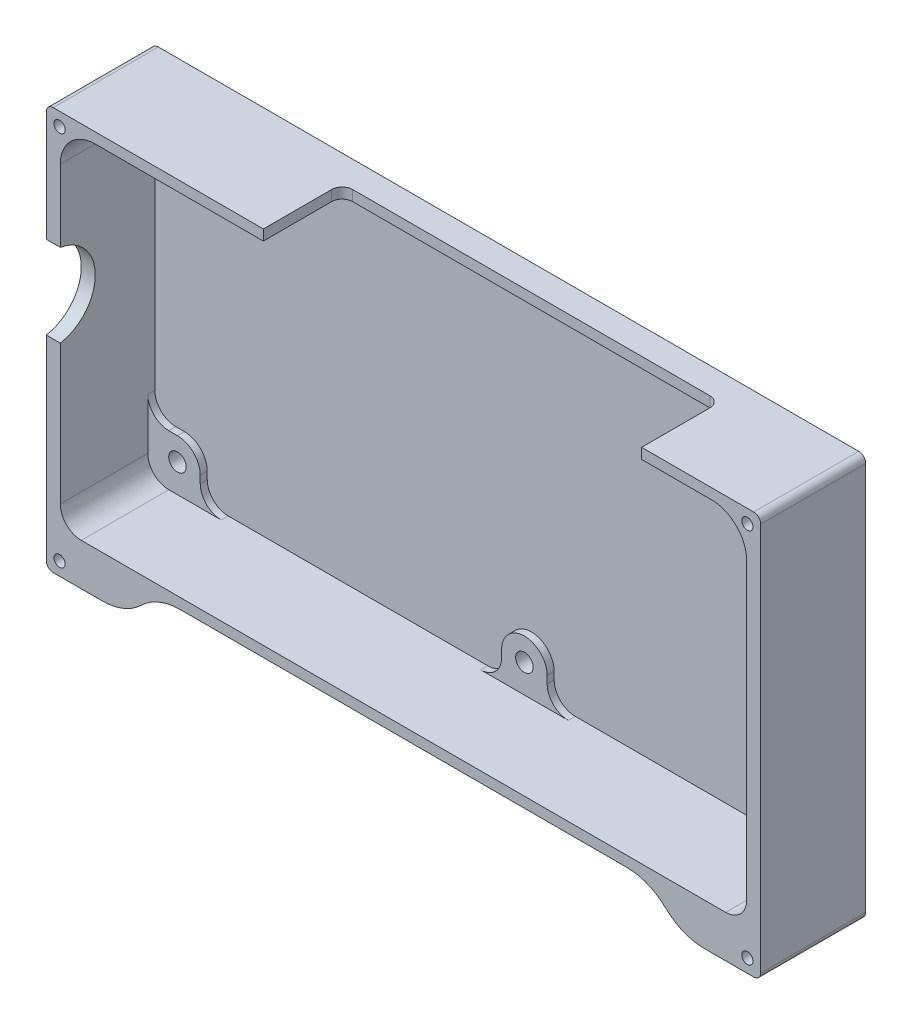
SolidWorks part; units mm, degrees
ref_plane "Ebene vorne" through (0, 0, 0) normal (0, 0, 1) x (1, 0, 0)
ref_plane "Ebene oben" through (0, 0, 0) normal (0, 1, 0) x (1, 0, 0)
ref_plane "Ebene rechts" through (0, 0, 0) normal (1, 0, 0) x (0, 0, -1)
sketch "Skizze1" plane through (0, 0, 0) normal (0, 0, 1) x (1, 0, 0)
  line L1 (0, 0) -> (102, 0)
  line L2 (0, 0) -> (0, 57.5)
  line L3 (0, 57.5) -> (102, 57.5)
  line L4 (102, 0) -> (102, 57.5)
  line L5 (2, 56) -> (100, 56) construction
  line L6 (2, 56) -> (2, 6)
  line L7 (2, 6) -> (100, 6) construction
  line L8 (100, 56) -> (100, 6) construction
  dimension "D1" = 2
  dimension "D2" = 2
  dimension "D3" = 1.5
  dimension "D4" = 6
  dimension "D5" = 50
  dimension "D6" = 98
extrude "Aufsatz-Linear austragen1" add sketch "Skizze1" along normal blind 15 contours L8 L5 L6 L7 | L2 L3 L4 L1
sketch "Skizze4" plane through (0, 0, 15) normal (0, 0, 1) x (1, 0, 0)
  line L0 (0, 57.5) -> (102, 57.5) construction
  line L1 (2, 56) -> (100, 56)
  line L2 (2, 56) -> (2, 6)
  line L3 (2, 6) -> (100, 6)
  line L4 (100, 56) -> (100, 6)
  line L5 (0, 0) -> (0, 57.5) construction
  line L6 (102, 0) -> (102, 57.5) construction
  line L7 (0, 0) -> (102, 0) construction
  dimension "D1" = 1.5
  dimension "D2" = 2
  dimension "D3" = 2
  dimension "D4" = 6
extrude "Schnitt-Linear austragen1" cut sketch "Skizze4" against normal blind 13.5
sketch "Skizze5" plane through (0, 0, 1.5) normal (0, 0, 1) x (1, 0, 0)
  line L0 (2, 6) -> (100, 6) construction
  line L2 (98.945, 55.13) -> (98.945, 56) construction
  line L3 (3.055, 6.87) -> (98.945, 6.87) construction
  line L4 (3.055, 6.87) -> (3.055, 55.13) construction
  line L5 (3.055, 55.13) -> (98.945, 55.13) construction
  line L6 (98.945, 6.87) -> (98.945, 55.13) construction
  line L7 (100, 56) -> (2, 56) construction
  line L8 (98.945, 6.87) -> (98.945, 6) construction
  line L9 (3.055, 55.13) -> (2, 55.13) construction
  line L10 (2, 56) -> (2, 6) construction
  line L11 (98.945, 55.13) -> (100, 55.13) construction
  line L12 (100, 6) -> (100, 56) construction
  line L13 (6.235, 10.05) -> (55.765, 10.05) construction
  line L14 (55.765, 10.05) -> (95.765, 10.05) construction
  line L15 (95.765, 10.05) -> (95.765, 51.95) construction
  line L16 (95.765, 51.95) -> (6.235, 51.95) construction
  line L17 (6.235, 51.95) -> (6.235, 10.05) construction
  circle A0 centre (6.235, 10.05) radius 3.25
  circle A1 centre (55.765, 10.05) radius 3.25
  circle A2 centre (95.765, 10.05) radius 3.25
  circle A3 centre (95.765, 51.95) radius 3.25
  circle A4 centre (6.235, 51.95) radius 3.25
  dimension "D8" = 6.5
  dimension "D1" = 3.18
  dimension "D2" = 3.18
  dimension "D3" = 92.71
  dimension "D4" = 95.89
  dimension "D5" = 48.26
  dimension "D6" = 52.71
  dimension "D7" = 3.18
extrude "Aufsatz-Linear austragen2" add sketch "Skizze5" along normal blind 1
sketch "Skizze10" plane through (0, 0, 15) normal (0, 0, 1) x (1, 0, 0)
  line L0 (8, 0) -> (94, 0)
  line L1 (0, 0) -> (102, 0) construction
  line L2 (19.1243, 4.5) -> (82.8757, 4.5)
  line L3 (2, 6) -> (100, 6) construction
  arc A0 (8, 0) -> (13.5621, 2.25) centre (8, 8) ccw
  arc A1 (19.1243, 4.5) -> (13.5621, 2.25) centre (19.1243, -3.5) ccw
  arc A2 (88.4379, 2.25) -> (82.8757, 4.5) centre (82.8757, -3.5) ccw
  arc A3 (88.4379, 2.25) -> (94, 0) centre (94, 8) ccw
  dimension "D4" = 8
  dimension "D1" = 8
  dimension "D2" = 8
  dimension "D3" = 1.5
extrude "Schnitt-Linear austragen2" cut sketch "Skizze10" against normal through all
sketch "Skizze11" plane through (0, 0, 0) normal (-1, 0, 0) x (0, 0, 1)
  line L0 (15, 0) -> (15, 57.5) construction
  line L2 (16, 40.8) -> (16, 28.8)
  line L5 (2.5, 48.7) -> (2.5, 55.2) construction
  line L6 (2.5, 48.7) -> (2.5, 55.2) construction
  arc A0 (16, 40.8) -> (16, 28.8) centre (16, 34.8) ccw
  point P11 (2.5, 51.95)
  dimension "D1" = 6
  dimension "D2" = 17.15
  dimension "D3" = 1
extrude "Schnitt-Linear austragen3" cut sketch "Skizze11" against normal up to next
sketch "Skizze12" plane through (0, 57.5, 0) normal (0, 1, 0) x (1, 0, 0)
  line L0 (85, -5.25) -> (85, -15)
  line L1 (0, -15) -> (102, -15) construction
  line L2 (85, -15) -> (31, -15)
  line L3 (31, -15) -> (31, -5.25)
  line L4 (32.5, -3.75) -> (83.5, -3.75)
  line L6 (92.515, -2.5) -> (99.015, -2.5) construction
  line L7 (92.515, -2.5) -> (99.015, -2.5) construction
  arc A0 (31, -5.25) -> (32.5, -3.75) centre (32.5, -5.25) cw
  arc A1 (85, -5.25) -> (83.5, -3.75) centre (83.5, -5.25) ccw
  point P11 (95.765, -2.5)
  dimension "D1" = 1.5
  dimension "D2" = 10.765
  dimension "D3" = 54
  dimension "D4" = 11.25
extrude "Schnitt-Linear austragen4" cut sketch "Skizze12" against normal up to next
sketch "Skizze13" plane through (0, 0, 1.5) normal (0, 0, 1) x (1, 0, 0)
  line L0 (6.235, 48.7) -> (2, 48.7)
  line L1 (9.485, 51.95) -> (9.485, 56)
  line L2 (9.485, 10.05) -> (9.485, 6)
  line L3 (6.235, 13.3) -> (2, 13.3)
  line L4 (2, 56) -> (2, 6)
  line L5 (2, 6) -> (100, 6)
  line L6 (100, 6) -> (100, 56)
  line L7 (100, 56) -> (2, 56)
  line L8 (2, 56) -> (2, 48.7)
  line L9 (2, 6) -> (9.485, 6)
  line L10 (100, 6) -> (100, 13.3)
  line L11 (100, 56) -> (92.515, 56)
  line L12 (59.015, 10.05) -> (59.015, 6)
  line L13 (52.515, 10.05) -> (52.515, 6)
  line L14 (95.765, 13.3) -> (100, 13.3)
  line L15 (92.515, 10.05) -> (92.515, 6)
  line L16 (92.515, 51.95) -> (92.515, 56)
  line L17 (95.765, 48.7) -> (100, 48.7)
  line L18 (9.485, 56) -> (2, 56)
  line L19 (100, 48.7) -> (100, 56)
  line L20 (92.515, 6) -> (100, 6)
  line L21 (52.515, 6) -> (59.015, 6)
  line L22 (2, 13.3) -> (2, 6)
  circle A0 centre (6.235, 51.95) radius 3.25 construction
  arc A1 (6.235, 48.7) -> (9.485, 51.95) centre (6.235, 51.95) ccw
  circle A2 centre (6.235, 10.05) radius 3.25 construction
  arc A3 (9.485, 10.05) -> (6.235, 13.3) centre (6.235, 10.05) ccw
  circle A4 centre (95.765, 10.05) radius 3.25 construction
  circle A5 centre (55.765, 10.05) radius 3.25 construction
  arc A6 (95.765, 13.3) -> (92.515, 10.05) centre (95.765, 10.05) ccw
  arc A7 (59.015, 10.05) -> (52.515, 10.05) centre (55.765, 10.05) ccw
  circle A8 centre (95.765, 51.95) radius 3.25 construction
  arc A9 (92.515, 51.95) -> (95.765, 48.7) centre (95.765, 51.95) ccw
  dimension "D1" = 0
extrude "Aufsatz-Linear austragen3" add sketch "Skizze13" along normal up to surface (1 mm away) up to face at (9.485, 51.95, 2.5)
hole_wizard "M3 Gewindebohrung1" positions "Skizze9" profile "Skizze8" tap size "M3" standard "DIN" end condition through all
sketch "Skizze9" plane through (0, 0, 2.5) normal (0, 0, 1) x (1, 0, 0)
  point P0 (6.235, 51.95)
  point P3 (6.235, 10.05)
  point P6 (55.765, 10.05)
  point P9 (95.765, 51.95)
  point P12 (95.765, 10.05)
sketch "Skizze8" plane through (6.235, 51.95, 2.5) normal (1, 0, 0) x (0, -1, 0)
  line L0 (0, 0) -> (0, 2.5)
  line L1 (0, 2.5) -> (1.25, 2.5)
  line L2 (1.25, 2.5) -> (1.25, 0)
  line L5 (1.25, 0) -> (0, 0)
  line L11 (0, -6.35) -> (0, 107.95) construction
  dimension "Bohrerdurchmesser" = 2.5
  dimension "Bohrungstiefe" = 2.5
cosmetic thread "Bohrungsgewinde3" parameters "D2"=3
cosmetic thread "Bohrungsgewinde4" parameters "D2"=3
cosmetic thread "Bohrungsgewinde5" parameters "D2"=3
cosmetic thread "Bohrungsgewinde6" parameters "D2"=3
cosmetic thread "Bohrungsgewinde7" parameters "D2"=3
hole_wizard "Gewindebohrung für M4x0.7 Helicoil1" positions "Skizze7" profile "Skizze6" tap size "M4x0.7" standard "Helicoil® Metrisch"
sketch "Skizze7" plane through (0, 0, 0) normal (0, -1, 0) x (-1, 0, 0)
  line L0 (-4, -4) -> (-98, -4)
  line L4 (0, 0) -> (-8, 0) construction
  line L5 (0, -15) -> (0, 0) construction
  line L6 (-102, -15) -> (-102, 0) construction
  point P0 (-4, -4)
  point P2 (-98, -4)
  dimension "D1" = 4
  dimension "D2" = 4
  dimension "D3" = 4
cosmetic thread "Bohrungsgewinde1" parameters "D1"=4, "D2"=5.007
cosmetic thread "Bohrungsgewinde2" parameters "D1"=4, "D2"=5.007
sketch "Skizze6" plane through (4, 0, 4) normal (1, 0, 0) x (0, 0, -1)
  line L0 (0, 0) -> (0, 5.2618)
  line L1 (0, 5.2618) -> (2.1, 4)
  line L2 (2.1, 4) -> (2.1, 0)
  line L5 (2.1, 0) -> (0, 0)
  line L10 (0, 5.2618) -> (-2.1, 4) construction
  line L11 (0, -6.35) -> (0, 107.95) construction
  dimension "Bohrerdurchmesser" = 4.2
  dimension "Bohrungstiefe" = 4
  dimension "Spitzenwinkel" = 118
fillet "Verrundung1" radius 3 2 edges at (2, 6, 8.75) (100, 6, 8.75)
fillet "Verrundung2" radius 3 10 edges at (92.515, 56, 2) (100, 48.7, 2) (100, 13.3, 2) (92.515, 6, 2) (59.015, 6, 2) (52.515, 6, 2) (2, 13.3, 2) (9.485, 6, 2) (2, 48.7, 2) (9.485, 56, 2)
fillet "Verrundung3" radius 1 4 edges at (0, 57.5, 7.5) (102, 57.5, 7.5) (102, 0, 7.5) (0, 0, 7.5)
ref_plane "Ebene1" through (51, 0, 0) normal (-1, 0, 0) x (0, 0, 1)
sketch "Skizze15" plane through (0, 0, 15) normal (0, 0, 1) x (1, 0, 0)
  line L0 (2, 56) -> (6, 56)
  line L1 (31, 56) -> (2, 56) construction
  line L2 (3, 53) -> (3, 50.1538) construction
  line L3 (2, 49.6834) -> (2, 56)
  line L4 (2, 56) -> (2, 40.7161) construction
  line L5 (51, 71.8353) -> (51, 15.7514) construction
  line L6 (51, 8.25) -> (51, -8.25) construction
  arc A0 (3, 53) -> (6, 56) centre (6, 53) cw
  arc A1 (2.5, 51.3417) -> (3, 53) centre (0, 53) ccw
  arc A2 (2, 49.6834) -> (2.5, 51.3417) centre (5, 49.6834) cw
  dimension "D1" = 3
  dimension "D2" = 1
extrude "Aufsatz-Linear austragen4" [suppressed] add sketch "Skizze15" against normal up to next
fillet "Verrundung4" radius 5 2 edges at (100, 56, 8.75) (2, 56, 8.75)
hole_wizard "M2 Gewindebohrung1" positions "Skizze18" profile "Skizze17" tap size "M2" standard "DIN"
sketch "Skizze18" plane through (0, 0, 15) normal (0, 0, 1) x (1, 0, 0)
  line L0 (1, 57.5) -> (31, 57.5) construction
  line L1 (0, 40.7161) -> (0, 56.5) construction
  line L2 (85, 57.5) -> (101, 57.5) construction
  line L3 (102, 1) -> (102, 56.5) construction
  line L4 (94, 0) -> (101, 0) construction
  line L5 (0, 1) -> (0, 28.8839) construction
  line L6 (1, 0) -> (8, 0) construction
  circle A0 centre (1.9, 55.6) radius 1.9
  circle A1 centre (100.1, 55.6) radius 1.9
  circle A2 centre (100.1, 1.9) radius 1.9
  circle A3 centre (1.9, 1.9) radius 1.9
  point P1 (1.9, 55.6)
  point P11 (100.1, 55.6)
  point P13 (100.1, 1.9)
  point P15 (1.9, 1.9)
  dimension "D1" = 3.8
sketch "Skizze17" plane through (1.9, 55.6, 15) normal (1, 0, 0) x (0, -1, 0)
  line L0 (0, 0) -> (0, 6.4807)
  line L1 (0, 6.4807) -> (0.8, 6)
  line L2 (0.8, 6) -> (0.8, 0)
  line L5 (0.8, 0) -> (0, 0)
  line L10 (0, 6.4807) -> (-0.8, 6) construction
  line L11 (0, -6.35) -> (0, 107.95) construction
  dimension "Bohrerdurchmesser" = 1.6
  dimension "Bohrungstiefe" = 6
  dimension "Spitzenwinkel" = 118
cosmetic thread "Bohrungsgewinde8" parameters "D1"=4, "D2"=2
cosmetic thread "Bohrungsgewinde9" parameters "D1"=4, "D2"=2
cosmetic thread "Bohrungsgewinde10" parameters "D1"=4, "D2"=2
cosmetic thread "Bohrungsgewinde11" parameters "D1"=4, "D2"=2
